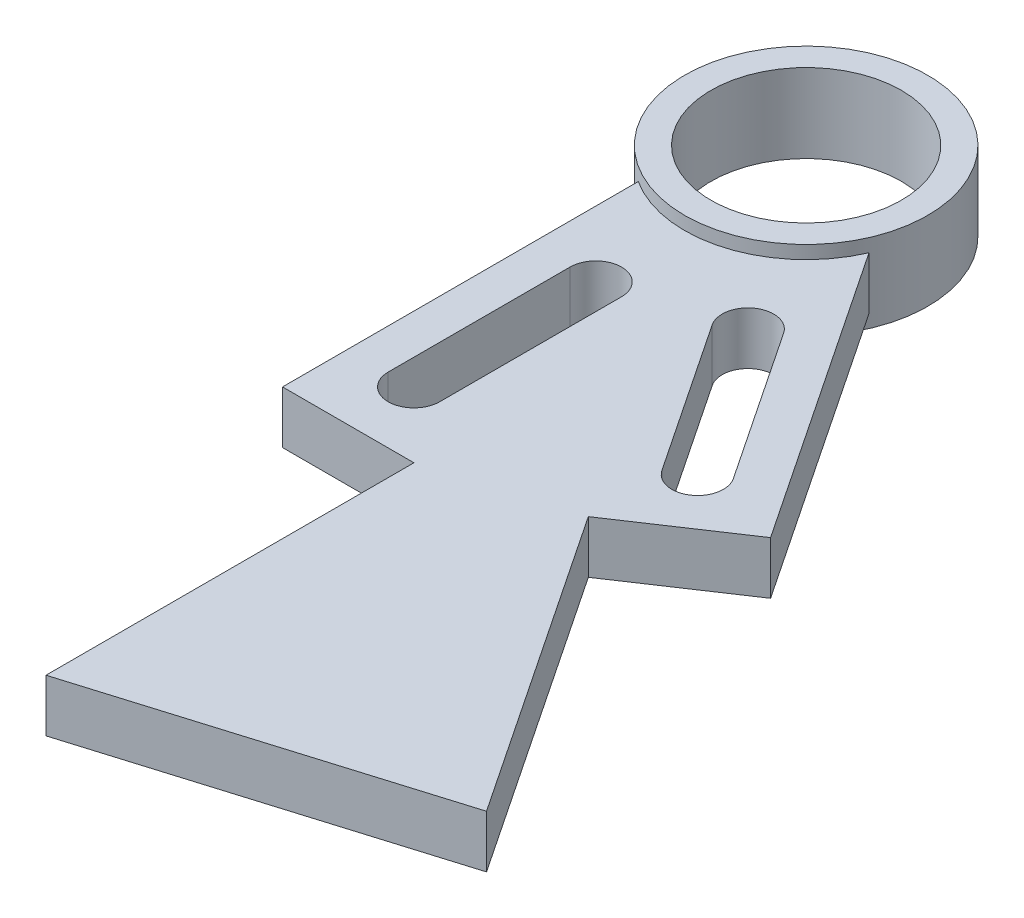
SolidWorks part; units mm, degrees
material "AISI 4130 Steel, normalized at 870C"
ref_plane "Front Plane" through (0, 0, 0) normal (0, 0, 1) x (1, 0, 0)
ref_plane "Top Plane" through (0, 0, 0) normal (0, 1, 0) x (1, 0, 0)
ref_plane "Right Plane" through (0, 0, 0) normal (1, 0, 0) x (0, 0, -1)
sketch "Sketch1" plane through (0, 0, 0) normal (0, 1, 0) x (1, 0, 0)
  line L0 (0, -50.4952) -> (0, -14.6812) construction
  line L1 (28.0293, -42.0015) -> (8.1494, -12.2117) construction
  line L2 (0, -47.3837) -> (0, -25.4127) construction
  line L5 (-3.1115, -47.3837) -> (-3.1115, -25.4127)
  line L8 (-7.9375, -55.3212) -> (7.9375, -55.3212)
  line L9 (24.1058, -50.4217) -> (37.3105, -41.6097)
  line L10 (-7.9375, -55.3212) -> (-7.9375, -12.3505)
  line L11 (37.3105, -41.6097) -> (13.4579, -5.867)
  line L12 (7.9375, -55.3212) -> (7.9375, -99.7712)
  line L13 (24.1058, -50.4217) -> (48.7795, -87.3948)
  line L14 (7.9375, -99.7712) -> (48.7795, -87.3948)
  line L15 (0, -14.6812) -> (0, 0) construction
  line L16 (0, -55.3212) -> (0, -50.4952) construction
  line L17 (30.7082, -46.0157) -> (28.0293, -42.0015)
  line L18 (3.1115, -47.3837) -> (3.1115, -25.4127)
  line L19 (14.1063, -21.1381) -> (26.3021, -39.4134) construction
  line L20 (16.6944, -19.4109) -> (28.8903, -37.6862)
  line L21 (11.5182, -22.8652) -> (23.714, -41.1405)
  line L22 (8.1494, -12.2117) -> (0, 0) construction
  line L23 (0, 0) -> (19.1521, -63.2019) construction
  line L25 (178.6057, -267.638) -> (14.5398, -21.7877) construction
  line L27 (0, 0) -> (28.3585, -93.583) construction
  circle A0 centre (0, 0) radius 11.5062
  circle A1 centre (0, 0) radius 14.6812
  arc A2 (-3.1115, -47.3837) -> (3.1115, -47.3837) centre (0, -47.3837) ccw
  arc A3 (3.1115, -25.4127) -> (-3.1115, -25.4127) centre (0, -25.4127) ccw
  arc A4 (16.6944, -19.4109) -> (11.5182, -22.8652) centre (14.1063, -21.1381) ccw
  arc A5 (23.714, -41.1405) -> (28.8903, -37.6862) centre (26.3021, -39.4134) ccw
  point P9 (0, -36.3982)
  point P14 (20.2042, -30.2757)
  point P23 (0, -55.3212)
  point P26 (30.7082, -46.0157)
  point P33 (0, -50.4952)
  point P36 (28.0293, -42.0015)
  point P38 (0, -22.3012)
  dimension "D2" = 29.3624
  dimension "D3" = 40.64
  dimension "D4" = 4.826
  dimension "D6" = 44.45
  dimension "D7" = 7.9375
  dimension "D5" = 4.826
  dimension "D8" = 7.62
  dimension "D9" = 66.04
extrude "Bearing extrude" add sketch "Sketch1" along normal mid plane 9.525 contours A1 A0 region at (-6.8368, 0, -12.521)
extrude "Boss-Extrude2" add sketch "Sketch1<5>" along normal mid plane 6.35 contours A1 L10 L8 L12 L14 L13 L9 L11 A4 A2 region at (17.0045, 0, 56.1148)
sketch "Sketch1<5>" plane through (0, 0, 0) normal (0, 1, 0) x (1, 0, 0) same geometry as "Sketch1"
sketch3d "Tab Point"
  line L0 (19.1521, 0, 63.2019) -> (19.1521, 25.4, 63.2019) construction
  line L1 (0, 0, 0) -> (19.1521, 0, 63.2019) construction
  line L2 (0, 0, 0) -> (28.3585, 0, 93.583) construction
  dimension "D1" = 25.4
equation "\"Apex_thickness\"= .25"
equation "\"Bearing_diameter\"= .906"
equation "\"A-arm_angle\"= 32.91"
equation "\"D1@Sketch1\"=\"Bearing_diameter\""
equation "\"D1@Boss-Extrude2\"= \"Apex_thickness\""
equation "\"apex slot\"= 1.4"
equation "\"tube diameter\"= 5 / 8"
